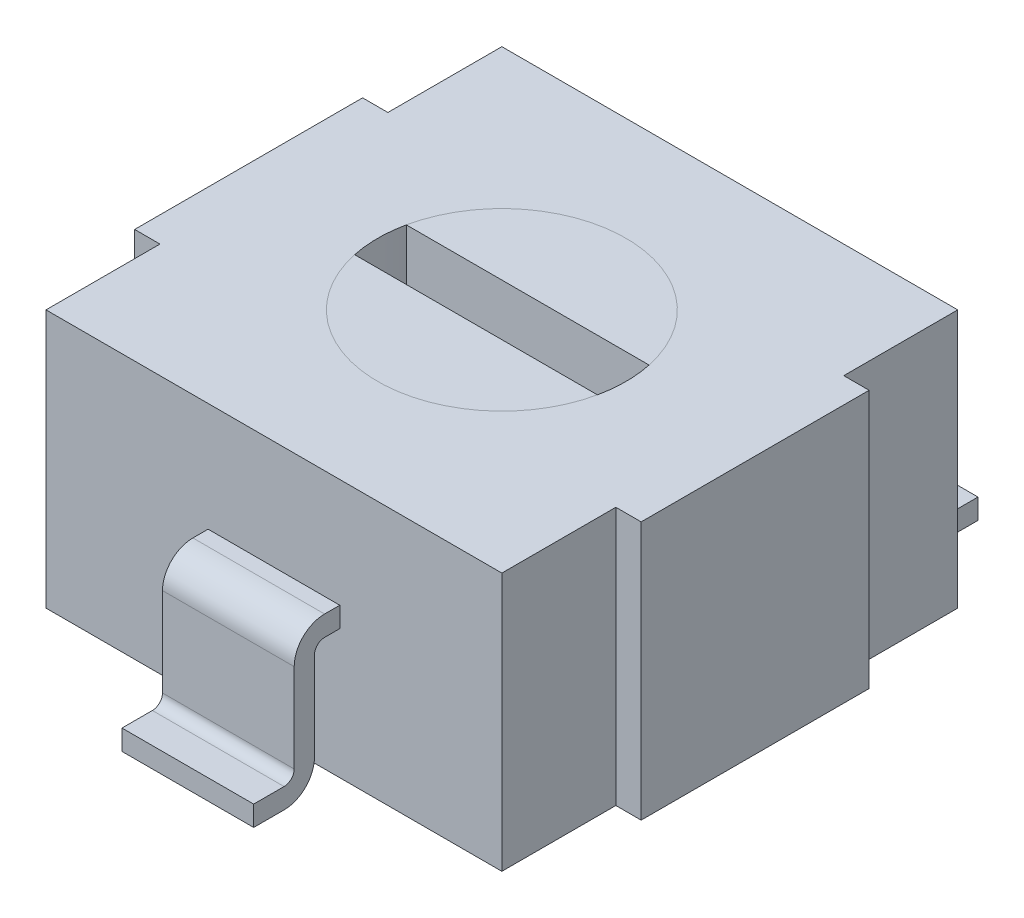
SolidWorks part; units mm, degrees
ref_plane "front" through (0, 0, 0) normal (0, 0, 1) x (1, 0, 0)
ref_plane "top" through (0, 0, 0) normal (0, 1, 0) x (1, 0, 0)
ref_plane "right" through (0, 0, 0) normal (1, 0, 0) x (0, 0, -1)
sketch "Sketch1" plane through (0, 0, 0) normal (0, 1, 0) x (1, 0, 0)
  line L0 (0, 0) -> (0, 2.25) construction
  line L1 (0, 0) -> (2.25, 0) construction
  line L3 (-2.25, -2.25) -> (2.25, -2.25)
  line L4 (-2.25, -2.25) -> (-2.25, 2.25)
  line L5 (-2.25, 2.25) -> (2.25, 2.25)
  line L6 (2.25, -2.25) -> (2.25, 2.25)
  dimension "D1" = 4.5
extrude "Base-Extrude" add sketch "Sketch1" along normal blind 2.55
sketch "Sketch2" plane through (0, 2.55, 0) normal (0, 1, 0) x (-1, 0, 0)
  line L0 (-2.25, 2.25) -> (-2.25, -2.25) construction
  line L1 (-2.25, 1.125) -> (-2.5, 1.125)
  line L2 (-2.25, 1.125) -> (-2.25, -1.125)
  line L3 (-2.25, -1.125) -> (-2.5, -1.125)
  line L4 (-2.5, 1.125) -> (-2.5, -1.125)
  line L5 (0, 0) -> (-2.25, 0) construction
  line L6 (0, 0) -> (0, -0.6425) construction
  line L7 (2.5, 1.125) -> (2.5, -1.125)
  line L8 (2.25, -1.125) -> (2.5, -1.125)
  line L9 (2.25, 1.125) -> (2.25, -1.125)
  line L10 (2.25, 1.125) -> (2.5, 1.125)
  dimension "D1" = 2.25
  dimension "D2" = 5
extrude "ears-Extrude1" add sketch "Sketch2" against normal through all
sketch "Sketch3" plane through (0, 0, 0) normal (1, 0, 0) x (0, 0, -1)
  line L0 (0, 0) -> (0, 1.2505) construction
  line L1 (3.1, 0) -> (2.5, 0)
  line L2 (2.5, 0) -> (2.5, 1.275)
  line L3 (2.5, 1.275) -> (2.25, 1.275)
  line L4 (2.25, 2.55) -> (2.25, 0) construction
  line L6 (1.125, 0) -> (2.25, 0) construction
  dimension "D1" = 6.2
  dimension "D2" = 0.6
extrude "double feet-Extrude-Thin1" add sketch "Sketch3" along normal mid plane 3.2 thin thin type one direction wall 0.2
sketch "Sketch4" plane through (0, 0, 0) normal (1, 0, 0) x (0, 0, -1)
  line L0 (2.5, 1.275) -> (2.25, 1.275) construction
  line L1 (2.5, 0) -> (2.5, 1.275) construction
  line L2 (3.1, 0) -> (2.5, 0) construction
  line L3 (2.5, 1.275) -> (2.25, 1.275) construction
  line L4 (2.5, 0) -> (2.5, 1.275) construction
  line L5 (3.1, 0) -> (2.5, 0) construction
  line L6 (0, 0) -> (0, 1.2505) construction
  line L7 (0, 0) -> (0, 1.2505) construction
  line L8 (-3.1, 0) -> (-2.5, 0)
  line L9 (-2.5, 0) -> (-2.5, 1.275)
  line L10 (-2.5, 1.275) -> (-2.25, 1.275)
extrude "single foot-Extrude-Thin2" add sketch "Sketch4" along normal mid plane 1.3 thin thin type one direction reverse wall 0.2
sketch "Sketch5" plane through (0, 2.55, 0) normal (0, 1, 0) x (-1, 0, 0)
  line L0 (0, 0) -> (0, -2.25) construction
  line L1 (-2.25, -2.25) -> (2.25, -2.25) construction
  line L2 (-0.8, -2.25) -> (0.8, -2.25)
  line L3 (-0.8, -2.25) -> (-0.8, -3.1)
  line L4 (-0.8, -3.1) -> (0.8, -3.1)
  line L5 (0.8, -2.25) -> (0.8, -3.1)
  line L6 (1.6, -2.4) -> (1.6, -2.25) construction
  line L7 (-1.6, -3.1) -> (1.6, -3.1) construction
  dimension "D1" = 0.8
extrude "remove middle of the double pins-Extrude1" cut sketch "Sketch5" against normal through all
sketch "Sketch6" plane through (0, 2.55, 0) normal (0, 1, 0) x (-1, 0, 0)
  circle A0 centre (0, 0) radius 1.225
  dimension "D1" = 2.45
split line "Split Line1"
sketch "Sketch7" plane through (0, 2.55, 0) normal (0, 1, 0) x (-1, 0, 0)
  line L0 (0, 0) -> (0, -0.255) construction
  line L1 (-1.1982, 0.255) -> (1.1982, 0.255)
  line L2 (-1.1982, 0.255) -> (-1.1982, -0.255) construction
  line L3 (-1.1982, -0.255) -> (1.1982, -0.255)
  line L4 (1.1982, 0.255) -> (1.1982, -0.255) construction
  line L5 (0, 0) -> (-1.1982, 0) construction
  circle A0 centre (0, 0) radius 1.225 construction
  arc A1 (1.1982, -0.255) -> (1.1982, 0.255) centre (0, 0) ccw
  arc A2 (-1.1982, 0.255) -> (-1.1982, -0.255) centre (0, 0) ccw
  dimension "D1" = 0.51
extrude "screw driver slot-Extrude2" cut sketch "Sketch7" against normal blind 0.51
